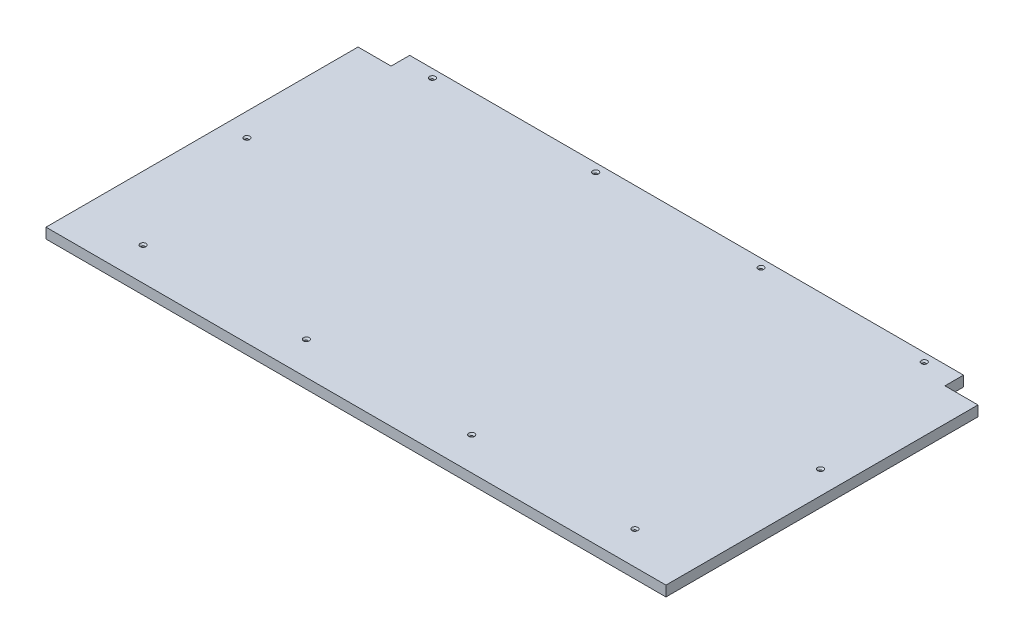
SolidWorks part; units mm, degrees
material "Cedar"
ref_plane "Front Plane" through (0, 0, 0) normal (0, 0, 1) x (1, 0, 0)
ref_plane "Top Plane" through (0, 0, 0) normal (0, 1, 0) x (1, 0, 0)
ref_plane "Right Plane" through (0, 0, 0) normal (1, 0, 0) x (0, 0, -1)
sketch "Sketch1" plane through (0, 0, 0) normal (0, 1, 0) x (1, 0, 0)
  line L1 (750, -400) -> (-750, -400)
  line L2 (750, -400) -> (750, 400)
  line L3 (750, 400) -> (-750, 400)
  line L4 (-750, -400) -> (-750, 400)
  line L5 (750, -400) -> (-750, 400) construction
  line L6 (750, 400) -> (-750, -400) construction
  point P0 (0, 0)
  dimension "D1" = 800
  dimension "D2" = 1500
extrude "RawMaterial" add sketch "Sketch1" along normal blind 25
sketch "Sketch2" plane through (0, 25, 0) normal (0, 1, 0) x (1, 0, 0)
  line L0 (750, 400) -> (-750, 400) construction
  line L1 (-761.4719, 422.6992) -> (-670, 422.6992)
  line L2 (-761.4719, 422.6992) -> (-761.4719, 355)
  line L3 (-761.4719, 355) -> (-670, 355)
  line L4 (-670, 422.6992) -> (-670, 355)
  line L5 (777.3454, 416.3957) -> (670, 416.3957)
  line L6 (777.3454, 416.3957) -> (777.3454, 355)
  line L7 (777.3454, 355) -> (670, 355)
  line L8 (670, 416.3957) -> (670, 355)
  line L9 (-750, 400) -> (-750, -400) construction
  line L10 (750, -400) -> (750, 400) construction
  line M5 (-750, 400) -> (-750, -400)
  line M7 (750, -400) -> (750, 400)
  line M8 (750, 400) -> (-750, 400)
  dimension "D1" = 45
  dimension "D2" = 80
  dimension "D3" = 80
extrude "SlotsForFrame" cut sketch "Sketch2" against normal through all contours L4 L3 M8 M5 | L8 L7 M8 M7 region at (710, 25, -377.5) region at (-710, 25, -377.5)
hole_wizard "M6 Clearance Hole frame mount" positions "Sketch4" profile "Sketch5" hole size "M6" standard "ANSI Metric" end condition through all
sketch "Sketch4" plane through (0, 25, 0) normal (0, -1, 0) x (-1, 0, 0)
  line L0 (750, -400) -> (-750, -400) construction
  line L1 (750, 355) -> (750, -400) construction
  line L2 (-750, -400) -> (-750, 355) construction
  point P0 (-595, -320)
  point P2 (-200, -320)
  point P4 (200, -320)
  point P6 (595, -320)
  point P10 (694, 30)
  point P14 (-694, 30)
  point P16 (-595, 380)
  point P18 (-200, 380)
  point P20 (200, 380)
  point P22 (595, 380)
  dimension "D1" = 80
  dimension "D2" = 155
  dimension "D3" = 155
  dimension "D4" = 395
  dimension "D5" = 400
  dimension "D6" = 780
  dimension "D7" = 56
  dimension "D8" = 1444
  dimension "D9" = 350
sketch "Sketch5" plane through (595, 25, 320) normal (1, 0, 0) x (0, 0, 1)
  line L0 (0, 0) -> (0, 25)
  line L1 (0, 25) -> (3.3, 25)
  line L2 (3.3, 25) -> (3.3, 3.7)
  line L3 (3.3, 3.7) -> (7, 0)
  line L5 (7, 0) -> (0, 0)
  line L6 (-3.3, 3.7) -> (-7, 0) construction
  line L11 (0, -6.35) -> (0, 107.95) construction
  dimension "Thru Hole Dia." = 6.6
  dimension "Thru Hole Depth" = 25
  dimension "Near C'Sink Dia." = 14
  dimension "Near C'Sink Angle" = 90
equation "\"D3@Sketch2\"=\"D2@Sketch2\""
equation "\"TableThickness\"= \"Thickness@RawMaterial\""
equation "\"D3@Sketch4\"=\"D2@Sketch4\""
